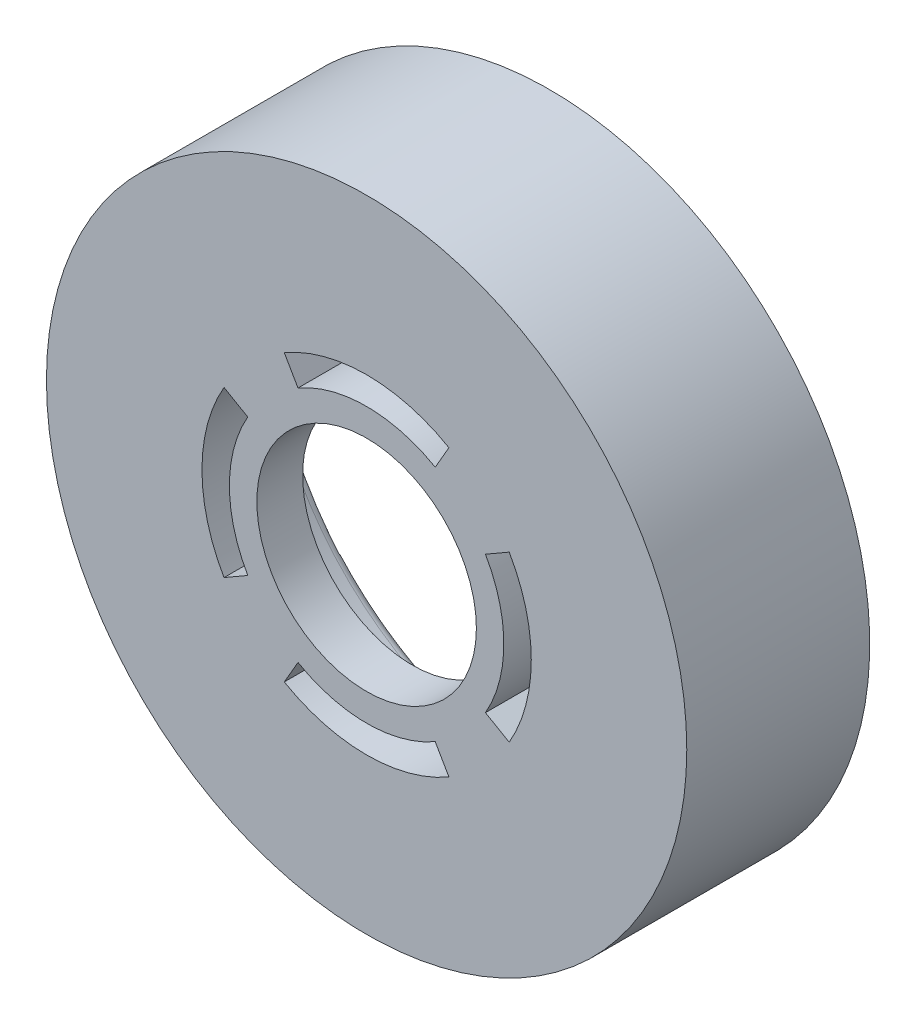
SolidWorks part; units mm, degrees
ref_plane "前视基准面" through (0, 0, 0) normal (0, 0, 1) x (1, 0, 0)
ref_plane "上视基准面" through (0, 0, 0) normal (0, 1, 0) x (1, 0, 0)
ref_plane "右视基准面" through (0, 0, 0) normal (1, 0, 0) x (0, 0, -1)
other "Configuration Table"
sketch "草图2" plane through (0, 0, 0) normal (0, 0, 1) x (1, 0, 0)
  circle A0 centre (0, 0) radius 35
  circle A1 centre (0, 0) radius 12
  dimension "D1" = 70
  dimension "D2" = 24
extrude "凸台-拉伸1" add sketch "草图2" along normal blind 5
sketch "草图3" plane through (0, 0, 0) normal (0, 0, -1) x (-1, 0, 0)
  circle A0 centre (0, 0) radius 30.05
  circle A1 centre (0, 0) radius 35
  dimension "D1" = 60.1
extrude "凸台-拉伸2" add sketch "草图3" along normal blind 15
sketch "草图4" plane through (0, 0, -15) normal (0, 0, -1) x (-1, 0, 0)
  line L0 (0, 0) -> (0, 32.5)
  line L1 (0, 0) -> (32.5, 0)
  line L2 (0, 0) -> (0, -32.5)
  line L3 (0, 0) -> (-32.5, 0)
  circle A0 centre (0, 32.5) radius 1.55
  circle A1 centre (32.5, 0) radius 1.55
  circle A2 centre (0, -32.5) radius 1.55
  circle A3 centre (-32.5, 0) radius 1.55
  point P9 (0, 0)
  point P17 (0, 0)
  dimension "D2" = 4
  dimension "D1" = 4
extrude "切除-拉伸1" cut sketch "草图4" against normal blind 10 contours A0 | A1 | A2 | A3 region at (1.065, 33.565, -15) region at (-32.5, 1.5062, -15) region at (-1.065, -31.435, -15) region at (34.0062, 0, -15)
fillet "圆角1" radius 1 1 edges at (-30.05, 0, -15)
sketch "草图5" plane through (0, 0, 0) normal (0, 0, -1) x (-1, 0, 0)
  line L0 (12.9904, -7.5) -> (15.5885, -9)
  line L1 (12.9904, 7.5) -> (15.5885, 9)
  line L2 (-7.5, 12.9904) -> (-9, 15.5885)
  line L3 (7.5, 12.9904) -> (9, 15.5885)
  line L4 (-7.5, -12.9904) -> (-9, -15.5885)
  line L5 (7.5, -12.9904) -> (9, -15.5885)
  line L6 (-12.9904, 7.5) -> (-15.5885, 9)
  line L7 (-12.9904, -7.5) -> (-15.5885, -9)
  arc A1 (7.5, 12.9904) -> (-7.5, 12.9904) centre (0, 0) ccw
  arc A2 (9, 15.5885) -> (-9, 15.5885) centre (0, 0) ccw
  arc A3 (12.9904, -7.5) -> (12.9904, 7.5) centre (0, 0) ccw
  arc A4 (15.5885, -9) -> (15.5885, 9) centre (0, 0) ccw
  arc A5 (-7.5, -12.9904) -> (7.5, -12.9904) centre (0, 0) ccw
  arc A6 (-9, -15.5885) -> (9, -15.5885) centre (0, 0) ccw
  arc A7 (-12.9904, 7.5) -> (-12.9904, -7.5) centre (0, 0) ccw
  arc A8 (-15.5885, 9) -> (-15.5885, -9) centre (0, 0) ccw
  point P21 (0, 0)
  dimension "D1" = 4
extrude "切除-拉伸2" cut sketch "草图5" against normal through all
